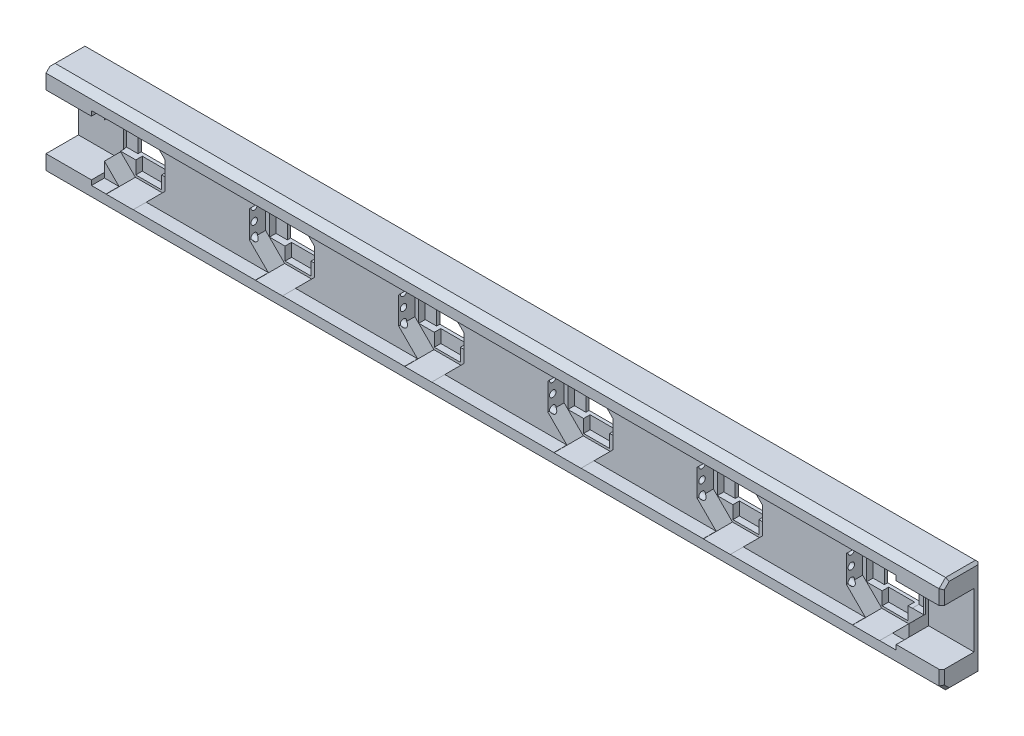
SolidWorks part; units mm, degrees
ref_plane "Front Plane" through (0, 0, 0) normal (0, 0, 1) x (1, 0, 0)
ref_plane "Top Plane" through (0, 0, 0) normal (0, 1, 0) x (1, 0, 0)
ref_plane "Right Plane" through (0, 0, 0) normal (1, 0, 0) x (0, 0, -1)
sketch "Sketch1" plane through (0, 0, 0) normal (0, 0, 1) x (1, 0, 0)
  line L1 (-91.75, 25.6543) -> (46.25, 25.6543)
  line L2 (-91.75, 25.6543) -> (-91.75, 10.6543)
  line L3 (-91.75, 10.6543) -> (46.25, 10.6543)
  line L4 (46.25, 25.6543) -> (46.25, 10.6543)
  dimension "D1" = 138
  dimension "D2" = 15
extrude "Boss-Extrude1" add sketch "Sketch1" along normal blind 6
sketch "Sketch12" plane through (46.25, 0, 0) normal (1, 0, 0) x (0, 0, -1)
  line L0 (-6, 25.6543) -> (-6, 24.6543)
  line L1 (-6, 10.6543) -> (-6, 25.6543) construction
  line L2 (-6, 24.6543) -> (-5, 25.6543)
  line L3 (-6, 25.6543) -> (0, 25.6543) construction
  line L4 (-5, 25.6543) -> (-6, 25.6543)
  line L5 (-6, 10.6543) -> (-5, 10.6543)
  line L6 (-6, 10.6543) -> (0, 10.6543) construction
  line L7 (-5, 10.6543) -> (-6, 11.6543)
  line L8 (-6, 10.6543) -> (-6, 25.6543) construction
  line L9 (-6, 11.6543) -> (-6, 10.6543)
  dimension "D1" = 1
  dimension "D2" = 1
  dimension "D3" = 1
extrude "Cut-Extrude8" cut sketch "Sketch12" against normal up to surface (138 mm away) up to face at (-91.75, 18.1543, 3)
sketch "Sketch13" plane through (0, 0, 0) normal (0, 0, -1) x (-1, 0, 0)
  line L0 (91.75, 25.6543) -> (91.75, 10.6543) construction
  line L1 (89.25, 23.1543) -> (89.75, 23.1543)
  line L2 (89.25, 23.1543) -> (89.25, 13.1543)
  line L3 (89.25, 13.1543) -> (89.75, 13.1543)
  line L4 (89.75, 23.1543) -> (89.75, 13.1543)
  line L5 (-46.25, 25.6543) -> (91.75, 25.6543) construction
  dimension "D1" = 2
  dimension "D2" = 0.5
  dimension "D3" = 10
  dimension "D4" = 2.5
extrude "Cut-Extrude9" cut sketch "Sketch13" against normal blind 0.6
fillet "Fillet1" radius 0.25 1 edges at (-89.75, 18.1543, 0)
fillet "Fillet2" radius 0.25 4 edges at (-89.5, 23.1543, 0.6) (-89.75, 18.1543, 0.6) (-89.5, 13.1543, 0.6) (-89.25, 18.1543, 0.6)
chamfer "Chamfer1" distance 0.4 angle 45 2 edges at (-22.75, 10.6543, 0) (-22.75, 25.6543, 0)
chamfer "Chamfer2" distance 0.4 angle 45 2 edges at (46.25, 18.1543, 0) (-91.75, 18.1543, 0)
chamfer "Chamfer3" distance 0.4 angle 45 2 edges at (-91.75, 10.6543, 2.7) (-91.75, 25.6543, 2.7)
chamfer "Chamfer5" distance 0.4 angle 45 5 edges at (46.25, 25.1543, 5.5) (46.25, 25.6543, 2.7) (46.25, 18.1543, 6) (46.25, 11.1543, 5.5) (46.25, 10.6543, 2.7)
sketch "Sketch15" plane through (0, 0, 6) normal (0, 0, 1) x (1, 0, 0)
  line L0 (-91.75, 24.6543) -> (-91.75, 11.6543) construction
  line L1 (-75.3821, 20.2328) -> (-78.3215, 23.1722)
  line L2 (-78.3215, 23.1722) -> (-82.4785, 23.1722)
  line L3 (-82.4785, 23.1722) -> (-85.4179, 20.2328)
  line L4 (-85.4179, 20.2328) -> (-85.4179, 16.0758)
  line L5 (-85.4179, 16.0758) -> (-82.4785, 13.1364)
  line L6 (-82.4785, 13.1364) -> (-78.3215, 13.1364)
  line L7 (-78.3215, 13.1364) -> (-75.3821, 16.0758)
  line L8 (-75.3821, 16.0758) -> (-75.3821, 20.2328)
  line L9 (-91.35, 25.6543) -> (45.85, 25.6543) construction
  line L10 (-91.75, 11.6543) -> (45.85, 11.6543) construction
  circle A0 centre (-80.4, 18.1543) radius 5.0179 construction
  dimension "D1" = 11.35
  dimension "D2" = 7.5
extrude "Cut-Extrude10" cut sketch "Sketch15" against normal blind 4.5
sketch "Sketch16" plane through (0, 0, 1.5) normal (0, 0, 1) x (1, 0, 0)
  line L1 (-83.0679, 20.7864) -> (-77.7679, 20.7864)
  line L2 (-83.0679, 20.7864) -> (-83.0679, 15.4864)
  line L3 (-83.0679, 15.4864) -> (-77.7679, 15.4864)
  line L4 (-77.7679, 20.7864) -> (-77.7679, 15.4864)
  line L5 (-85.4179, 20.2328) -> (-85.4179, 16.0758) construction
  line L6 (-82.4785, 13.1364) -> (-78.3215, 13.1364) construction
  point P4 (-83.0679, 18.1364)
  point P7 (-85.4179, 18.1543)
  point P10 (-80.4, 13.1364)
  point P11 (-80.4179, 15.4864)
  dimension "D1" = 5.3
  dimension "D2" = 5.3
  dimension "D3" = 2.35
  dimension "D4" = 2.35
extrude "Cut-Extrude11" cut sketch "Sketch16" against normal blind 4.5
sketch "Sketch17" plane through (0, 0, 1.5) normal (0, 0, 1) x (1, 0, 0)
  line L0 (-83.0679, 15.4864) -> (-77.7679, 15.4864) construction
  line L1 (-82.4179, 15.4864) -> (-78.4179, 15.4864)
  line L2 (-82.4179, 15.4864) -> (-82.4179, 13.4864)
  line L3 (-82.4179, 13.4864) -> (-78.4179, 13.4864)
  line L4 (-78.4179, 15.4864) -> (-78.4179, 13.4864)
  line L5 (-77.7679, 20.7864) -> (-83.0679, 20.7864) construction
  line L6 (-82.4179, 20.7864) -> (-78.4179, 20.7864)
  line L7 (-82.4179, 20.7864) -> (-82.4179, 22.7864)
  line L8 (-82.4179, 22.7864) -> (-78.4179, 22.7864)
  line L9 (-78.4179, 20.7864) -> (-78.4179, 22.7864)
  line L10 (-77.7679, 15.4864) -> (-77.7679, 20.7864) construction
  dimension "D1" = 4
  dimension "D2" = 4
  dimension "D3" = 2
  dimension "D4" = 2
  dimension "D5" = 0.65
  dimension "D6" = 0.65
extrude "Cut-Extrude12" cut sketch "Sketch17" against normal blind 1
sketch "Sketch18" plane through (0, 0, 1.5) normal (0, 0, 1) x (1, 0, 0)
  line L1 (-83.0679, 15.4864) -> (-84.8179, 15.4864)
  line L2 (-83.0679, 15.4864) -> (-83.0679, 20.8045)
  line L3 (-83.0679, 20.8045) -> (-84.8179, 20.8045)
  line L4 (-84.8179, 15.4864) -> (-84.8179, 20.8045)
  line L5 (-77.7679, 20.7864) -> (-76.0179, 20.7864)
  line L6 (-77.7679, 20.7864) -> (-77.7679, 15.5045)
  line L7 (-77.7679, 15.5045) -> (-76.0179, 15.5045)
  line L8 (-76.0179, 20.7864) -> (-76.0179, 15.5045)
  dimension "D1" = 1.75
  dimension "D2" = 1.75
extrude "Cut-Extrude13" cut sketch "Sketch18" against normal blind 1
pattern_linear "LPattern1" count 6 spacing 23 along (1, 0, 0) of "Cut-Extrude10", "Cut-Extrude11", "Cut-Extrude12", "Cut-Extrude13"
sketch "Sketch19" plane through (0, 0, 6) normal (0, 0, 1) x (1, 0, 0)
  line L0 (-91.75, 24.6543) -> (-91.75, 11.6543) construction
  line L1 (-91.75, 22.4043) -> (-84.75, 22.4043)
  line L2 (-91.75, 22.4043) -> (-91.75, 13.9043)
  line L3 (-91.75, 13.9043) -> (-84.75, 13.9043)
  line L4 (-84.75, 22.4043) -> (-84.75, 13.9043)
  line L6 (-91.35, 10.6543) -> (45.85, 10.6543) construction
  line L14 (46.25, 24.4886) -> (46.25, 11.82) construction
  line L15 (46.25, 22.4043) -> (39.25, 22.4043)
  line L16 (46.25, 22.4043) -> (46.25, 13.9043)
  line L17 (46.25, 13.9043) -> (39.25, 13.9043)
  line L18 (39.25, 22.4043) -> (39.25, 13.9043)
  dimension "D1" = 8.5
  dimension "D2" = 3.25
  dimension "D3" = 7
  dimension "D4" = 8.5
  dimension "D5" = 7
  dimension "D6" = 3.25
extrude "Cut-Extrude14" cut sketch "Sketch19" against normal blind 5
sketch "Sketch20" plane through (0, 0, 6) normal (0, 0, 1) x (1, 0, 0)
  line L0 (-91.35, 10.6543) -> (45.85, 10.6543) construction
  line L1 (39.25, 13.1543) -> (-84.75, 13.1543)
  line L2 (39.25, 13.1543) -> (39.25, 23.1543)
  line L3 (39.25, 23.1543) -> (-84.75, 23.1543)
  line L4 (-84.75, 13.1543) -> (-84.75, 23.1543)
  line L6 (-84.75, 20.9007) -> (-84.75, 22.4043) construction
  dimension "D1" = 10
  dimension "D2" = 2.5
  dimension "D3" = 0
extrude "Cut-Extrude15" cut sketch "Sketch20" against normal blind 2
sketch "Sketch21" plane through (-16.4179, 0, 0) normal (1, 0, 0) x (0, 0, -1)
  line L1 (-1.5, 20.2328) -> (-4, 20.2328) construction
  line L2 (-4, 16.0758) -> (-4, 20.2328) construction
  circle A0 centre (-3.25, 18.1628) radius 0.5
  circle A1 centre (-3.25, 20.1628) radius 0.5
  circle A2 centre (-3.25, 16.1628) radius 0.5
  dimension "D2" = 1
  dimension "D3" = 1
  dimension "D4" = 1
  dimension "D1" = 2.07
  dimension "D5" = 2
  dimension "D6" = 2
  dimension "D7" = 0.75
extrude "Cut-Extrude16" cut sketch "Sketch21" against normal through all both and the other way through all
